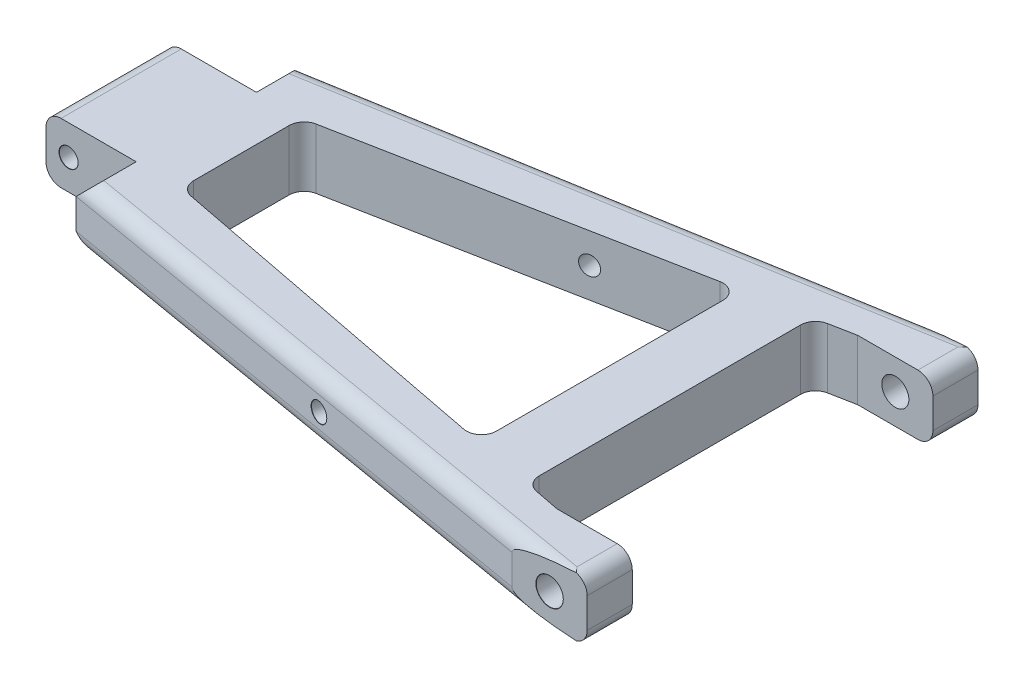
SolidWorks part; units mm, degrees
ref_plane "Front Plane" through (0, 0, 0) normal (0, 0, 1) x (1, 0, 0)
ref_plane "Top Plane" through (0, 0, 0) normal (0, 1, 0) x (1, 0, 0)
ref_plane "Right Plane" through (0, 0, 0) normal (1, 0, 0) x (0, 0, -1)
sketch "Sketch1" plane through (0, 0, 0) normal (0, 1, 0) x (1, 0, 0)
  line L0 (-55.9027, 0) -> (94.1519, 0) construction
  line L1 (0, -8) -> (0, 8) construction
  line L2 (0, 8) -> (-10, 8)
  line L5 (0, 14) -> (70, 26)
  line L6 (70, 26) -> (80, 26)
  line L7 (80, 26) -> (80, 20)
  line L8 (80, 20) -> (70, 20)
  line L9 (70, 20) -> (66.62, 19.3458)
  line L10 (8, 6.35) -> (8, -6.35)
  line L11 (65, 17.3822) -> (65, -17.3822)
  line L12 (54.62, 17.0232) -> (9.62, 8.3135)
  line L13 (57, -15.0597) -> (57, 15.0597)
  line L14 (-5, 26.3011) -> (-5, -14.3015) construction
  line L15 (75, 38.6076) -> (75, -13.767) construction
  line L16 (80, -26) -> (80, -20)
  line L17 (70, -26) -> (80, -26)
  line L18 (80, -20) -> (70, -20)
  line L19 (70, -20) -> (66.62, -19.3458)
  line L20 (54.62, -17.0232) -> (9.62, -8.3135)
  line L21 (0, -14) -> (70, -26)
  line L24 (0, -8) -> (-10, -8)
  line L25 (0, -14) -> (0, -8)
  line L26 (0, 8) -> (0, 14)
  line L27 (-10, 8) -> (-10, -8)
  arc A0 (66.62, 19.3458) -> (65, 17.3822) centre (67, 17.3822) ccw
  arc A1 (57, 15.0597) -> (54.62, 17.0232) centre (55, 15.0597) ccw
  arc A2 (9.62, 8.3135) -> (8, 6.35) centre (10, 6.35) ccw
  arc A3 (66.62, -19.3458) -> (65, -17.3822) centre (67, -17.3822) cw
  arc A4 (57, -15.0597) -> (54.62, -17.0232) centre (55, -15.0597) cw
  arc A5 (9.62, -8.3135) -> (8, -6.35) centre (10, -6.35) cw
  point P3 (-5, 8)
  point P22 (75, 20)
  point P31 (57, 17.4839)
  point P34 (8, 8)
  point P43 (65, 0)
  point P46 (57, 0)
  point P47 (8, 0)
  dimension "D9" = 2
  dimension "D2" = 40
  dimension "D3" = 16
  dimension "D4" = 10
  dimension "D5" = 6
  dimension "D6" = 10
  dimension "D7" = 80
  dimension "D8" = 5
  dimension "D10" = 8
  dimension "D11" = 8
  dimension "D12" = 28
extrude "Boss-Extrude1" add sketch "Sketch1" along normal mid plane 8
sketch "Sketch3" plane through (0, 0, 26) normal (0, 0, 1) x (1, 0, 0)
  line L0 (70, 4) -> (80, -4) construction
  circle A0 centre (75, 0) radius 1
  dimension "2" = 2
extrude "Cut-Extrude2" cut sketch "Sketch3" against normal through all
sketch "Sketch4" plane through (0, 0, 8) normal (0, 0, 1) x (1, 0, 0)
  line L0 (-10, 4) -> (0, -4) construction
  line L1 (-10, 4) -> (-10, -4) construction
  circle A0 centre (-7, 0) radius 1
  point P7 (-5, 0)
  dimension "D1" = 2
  dimension "D2" = 3
extrude "Cut-Extrude3" cut sketch "Sketch4" against normal through all
hole_wizard "Tap Drill for M3x0.5 Tap2" positions "Sketch9" profile "Sketch10" hole size "M3x0.5" standard "ANSI Metric" end condition through all
sketch "Sketch9" plane through (0, 0, 8) normal (0, 0, 1) x (1, 0, 0)
  point P0 (-7, 0)
sketch "Sketch10" plane through (-7, 0, 8) normal (1, 0, 0) x (0, -1, 0)
  line L0 (0, 0) -> (0, 34)
  line L1 (0, 34) -> (1.25, 34)
  line L2 (1.25, 34) -> (1.25, 0.025)
  line L3 (1.25, 0.025) -> (1.275, 0)
  line L5 (1.275, 0) -> (0, 0)
  line L6 (-1.25, 0.025) -> (-1.275, 0) construction
  line L11 (0, -6.35) -> (0, 107.95) construction
  dimension "Thru Hole Dia." = 2.5
  dimension "Thru Hole Depth" = 34
  dimension "Near C'Sink Dia." = 2.55
  dimension "Near C'Sink Angle" = 90
hole_wizard "M3 Clearance Hole2" positions "Sketch11" profile "Sketch12" hole size "M3" standard "ANSI Metric" end condition through all
sketch "Sketch11" plane through (0, 0, 26) normal (0, 0, 1) x (1, 0, 0)
  point P0 (75, 0)
sketch "Sketch12" plane through (75, 0, 26) normal (1, 0, 0) x (0, -1, 0)
  line L0 (0, 0) -> (0, 52)
  line L1 (0, 52) -> (1.8, 52)
  line L2 (1.8, 52) -> (1.8, 0.025)
  line L3 (1.8, 0.025) -> (1.825, 0)
  line L5 (1.825, 0) -> (0, 0)
  line L6 (-1.8, 0.025) -> (-1.825, 0) construction
  line L11 (0, -6.35) -> (0, 107.95) construction
  dimension "Thru Hole Dia." = 3.6
  dimension "Thru Hole Depth" = 52
  dimension "Near C'Sink Dia." = 3.65
  dimension "Near C'Sink Angle" = 90
fillet "Fillet1" radius 2 6 edges at (80, -4, 23) (80, -4, -23) (80, 4, -23) (80, 4, 23) (-10, -4, 0) (-10, 4, 0)
chamfer "Chamfer1" distance 2 angle 45 4 edges at (0, -4, -11) (0, 4, -11) (0, -4, 11) (0, 4, 11)
sketch "Sketch14" plane through (0, 0, 0) normal (0, 1, 0) x (1, 0, 0)
  line L0 (75, 3.6276) -> (75, -32.3724) construction
  line L1 (0, 0) -> (92.2268, 0) construction
  line L2 (39, 31.4045) -> (39, -30.3527) construction
  line L3 (73.2, 26) -> (73.2, 20)
  line L4 (76.8, 20) -> (76.8, 26)
  line L5 (76.8, 20) -> (76.8, 26) construction
  line L6 (73.2, 26) -> (73.2, 20) construction
  line L7 (73.2, 20) -> (76.8, 20) construction
  line L8 (54.62, 17.0232) -> (9.62, 8.3135) construction
  line L9 (9.62, -8.3135) -> (54.62, -17.0232) construction
  line L10 (70, 26) -> (2, 14.3429) construction
  line L11 (0, -14) -> (2, -14.3429) construction
  point P11 (75, 20)
  point P12 (39, 14)
  point P13 (39, -20.6857)
  point P16 (39, -14)
  point P19 (39, 20.6857)
  point P20 (0, 0)
  point P23 (0, 0)
  dimension "D1" = 36
hole_wizard "Tap Drill for M3x0.5 Tap4" positions "Sketch19" profile "Sketch20" hole size "M3x0.5" standard "ANSI Metric" end condition up to next
sketch "Sketch19" plane through (-2.3315, 0, 13.6003) normal (-0.169, 0, 0.9856) x (0.9856, 0, 0.169)
  point P0 (41.9344, 0)
sketch "Sketch20" plane through (39, 0, 20.6857) normal (0, 1, 0) x (0.9856, 0, 0.169)
  line L0 (0, 0) -> (0, 6.5654)
  line L1 (0, 6.5654) -> (1.25, 6.5654)
  line L2 (1.25, 6.5654) -> (1.25, 0.025)
  line L3 (1.25, 0.025) -> (1.275, 0)
  line L5 (1.275, 0) -> (0, 0)
  line L6 (-1.25, 0.025) -> (-1.275, 0) construction
  line L11 (0, -6.35) -> (0, 107.95) construction
  dimension "Thru Hole Dia." = 2.5
  dimension "Thru Hole Depth" = 6.5654
  dimension "Near C'Sink Dia." = 2.55
  dimension "Near C'Sink Angle" = 90
hole_wizard "Tap Drill for M3x0.5 Tap5" positions "Sketch21" profile "Sketch22" hole size "M3x0.5" standard "ANSI Metric" end condition up to next
sketch "Sketch21" plane through (-2.3315, 0, -13.6003) normal (-0.169, 0, -0.9856) x (-0.9856, 0, 0.169)
  point P0 (-41.9344, 0)
sketch "Sketch22" plane through (39, 0, -20.6857) normal (0, 1, 0) x (-0.9856, 0, 0.169)
  line L0 (0, 0) -> (0, 6.5654)
  line L1 (0, 6.5654) -> (1.25, 6.5654)
  line L2 (1.25, 6.5654) -> (1.25, 0.025)
  line L3 (1.25, 0.025) -> (1.275, 0)
  line L5 (1.275, 0) -> (0, 0)
  line L6 (-1.25, 0.025) -> (-1.275, 0) construction
  line L11 (0, -6.35) -> (0, 107.95) construction
  dimension "Thru Hole Dia." = 2.5
  dimension "Thru Hole Depth" = 6.5654
  dimension "Near C'Sink Dia." = 2.55
  dimension "Near C'Sink Angle" = 90
fillet "Fillet2" radius 2 4 edges at (36, -4, 20.1714) (36, 4, 20.1714) (36, -4, -20.1714) (36, 4, -20.1714)
